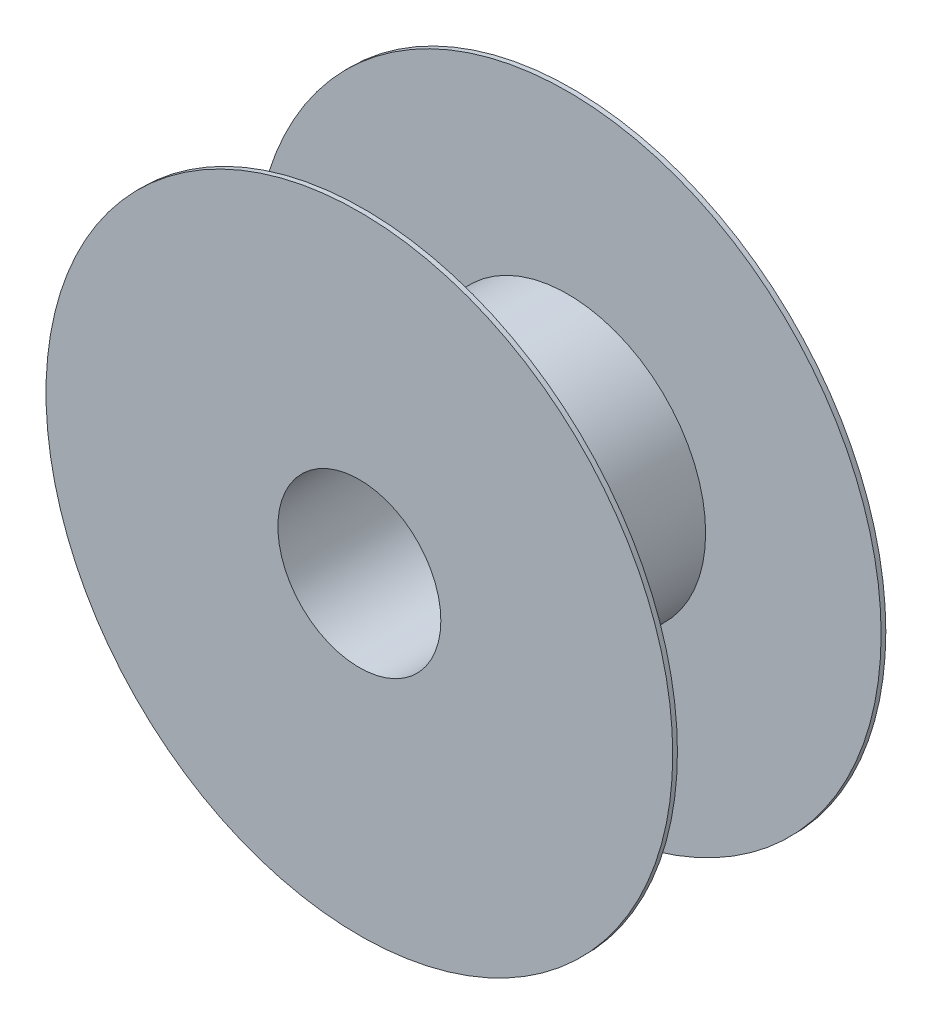
SolidWorks part; units mm, degrees
ref_plane "Plano frontal" through (0, 0, 0) normal (0, 0, 1) x (1, 0, 0)
ref_plane "Plano superior" through (0, 0, 0) normal (0, 1, 0) x (1, 0, 0)
ref_plane "Plano direito" through (0, 0, 0) normal (1, 0, 0) x (0, 0, -1)
sketch "Esboço1" plane through (0, 0, 0) normal (0, 0, 1) x (1, 0, 0)
  circle A0 centre (0, 0) radius 100
  circle A1 centre (0, 0) radius 26
  circle A2 centre (0, 0) radius 44
  dimension "D1" = 200
  dimension "D2" = 52
  dimension "D3" = 88
extrude "Ressalto-extrusão1" add sketch "Esboço1" against normal blind 1.5 contours A0 A2 | A2 A1 region at (-97.1716, 0, 0) region at (-42.7555, 0, 0)
extrude "Ressalto-extrusão2" add sketch "Esboço1<3>" against normal blind 34 contours A2 A1 region at (-42.7555, 0, 0)
sketch "Esboço1<3>" plane through (0, 0, 0) normal (0, 0, 1) x (1, 0, 0) same geometry as "Esboço1"
ref_plane "Plano1" through (0, 0, -34) normal (0, 0, -1) x (-1, 0, 0)
mirror "Espelhar1" about plane through (0, 0, -34) normal (0, 0, -1) of bodies 102
